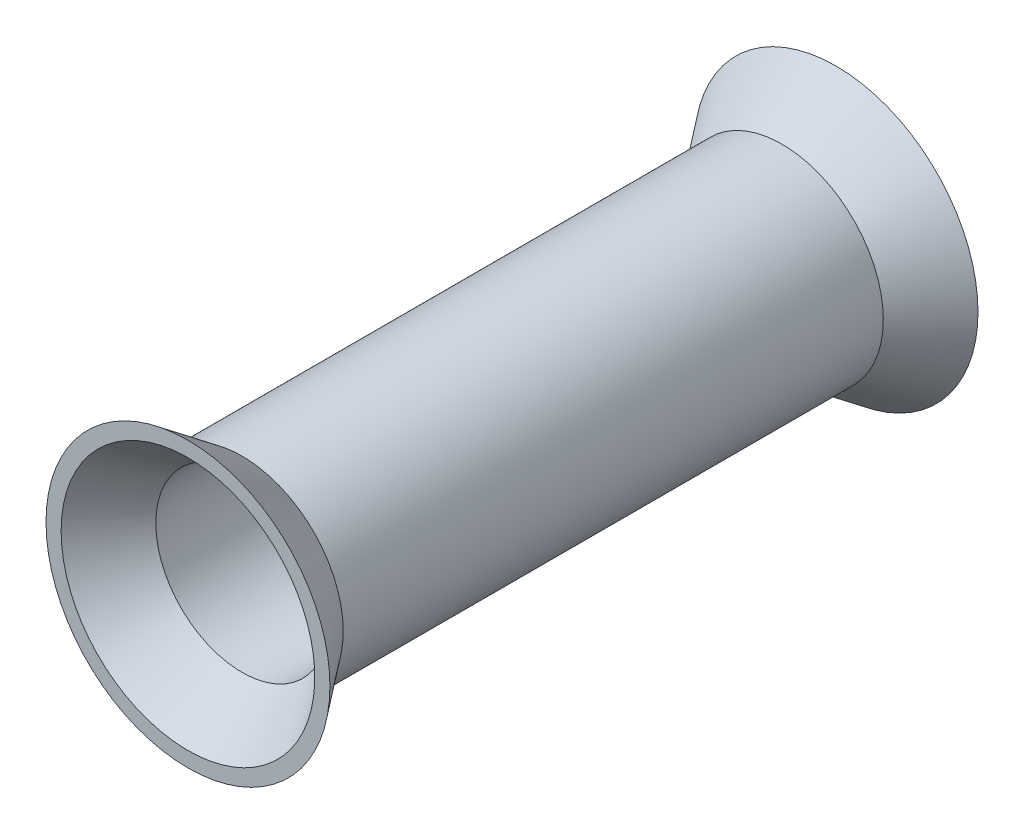
SolidWorks part; units mm, degrees
ref_plane "Front Plane" through (0, 0, 0) normal (0, 0, 1) x (1, 0, 0)
ref_plane "Top Plane" through (0, 0, 0) normal (0, 1, 0) x (1, 0, 0)
ref_plane "Right Plane" through (0, 0, 0) normal (1, 0, 0) x (0, 0, -1)
sketch "Sketch1" plane through (0, 0, 0) normal (0, 0, 1) x (1, 0, 0)
  line L0 (-4.7625, 0) -> (4.7625, 0) construction
  line L1 (0, 0) -> (0, 1.0456) construction
  point P0 (-4.0513, 0)
  point P4 (0, 0)
  point P6 (4.0513, 0)
  dimension "OD" = 9.525
  dimension "ID" = 8.1026
sketch "Sketch2" plane through (0, 0, 0) normal (0, 0, 1) x (1, 0, 0)
  line L0 (-4.7625, 0) -> (4.7625, 0) construction
  circle A0 centre (0, 0) radius 4.0513
  circle A1 centre (0, 0) radius 4.7625
  dimension "D1" = 8.1026
  dimension "D2" = 9.525
extrude "Boss-Extrude1" add sketch "Sketch2" along normal mid plane 25.4
sketch "Sketch3" plane through (0, 0, 0) normal (1, 0, 0) x (0, 0, -1)
  line L0 (12.7, 0) -> (-12.7, 0) construction
  line L1 (-12.7, 4.7625) -> (-12.7, -4.7625) construction
  line L2 (0, 0) -> (0, 21.8825) construction
  point P0 (-12.573, 0)
  point P6 (0, 0)
  point P8 (12.573, 0)
  dimension "D1" = 25.146
ref_axis "Center Axis 1" through (0, 0, 12.7) along (0, 0, -1)
ref_plane "Contact Plane 1" through (0, 0, 12.7) normal (0, 0, 1) x (1, 0, 0)
ref_plane "Contact Plane 2" through (0, 0, -12.7) normal (0, 0, -1) x (-1, 0, 0)
sketch "Sketch4" plane through (0, 0, -12.7) normal (0, 0, -1) x (-1, 0, 0)
  circle A1 centre (0, 0) radius 4.7625
  circle A4 centre (0, 0) radius 4.7625 construction
extrude "Boss-Extrude2" add sketch "Sketch4" along normal blind 2.54 draft 37 draft outward yes
sketch "Sketch5" plane through (0, 0, -15.24) normal (0, 0, -1) x (-1, 0, 0)
  line L0 (-4.7625, 0) -> (-4.0513, 0) construction
  line L1 (-6.6765, 0) -> (-5.9653, 0) construction
  circle A2 centre (0, 0) radius 4.7625 construction
  circle A3 centre (0, 0) radius 4.0513 construction
  circle A4 centre (0, 0) radius 5.9653
  circle A5 centre (0, 0) radius 6.6765 construction
extrude "Cut-Extrude2" cut sketch "Sketch5" against normal through all draft 37
mirror "Mirror1" about plane through (0, 0, 0) normal (0, 0, 1) of "Cut-Extrude2", "Boss-Extrude2"
equation "\"D1@Sketch2\"=\"ID@Sketch1\""
equation "\"D2@Sketch2\"=\"OD@Sketch1\""
equation "\"D1@Sketch3\"=\"Length@Boss-Extrude1\"*0.99"
